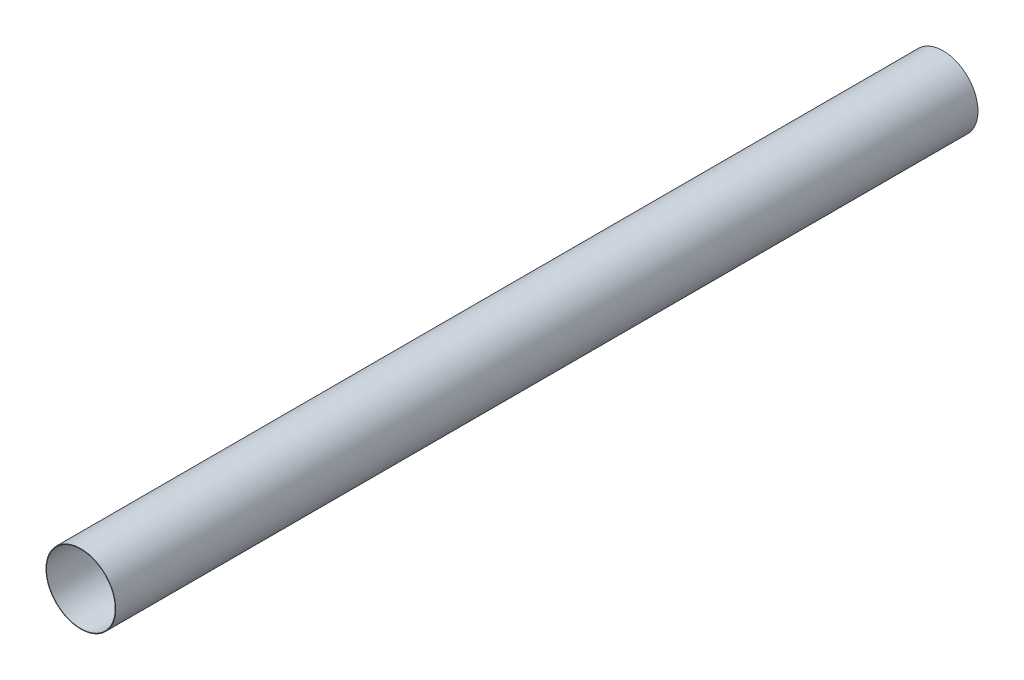
SolidWorks part; units mm, degrees
material "6061-T6 (SS)"
ref_plane "Front Plane" through (0, 0, 0) normal (0, 0, 1) x (1, 0, 0)
ref_plane "Top Plane" through (0, 0, 0) normal (0, 1, 0) x (1, 0, 0)
ref_plane "Right Plane" through (0, 0, 0) normal (1, 0, 0) x (0, 0, -1)
other "Center of Mass"
sketch "Sketch1" plane through (0, 0, 0) normal (0, 0, 1) x (1, 0, 0)
  circle A0 centre (0, 0) radius 72
  circle A1 centre (0, 0) radius 73
  dimension "D1" = 146
  dimension "D2" = 1
extrude "Boss-Extrude1" add sketch "Sketch1" along normal blind 1804
ref_plane "Mid-Plane" through (0, 0, 902) normal (0, 0, 1) x (1, 0, 0)
ref_axis "Axis1" through (0, 0, 1902.5) along (0, 0, -1)
